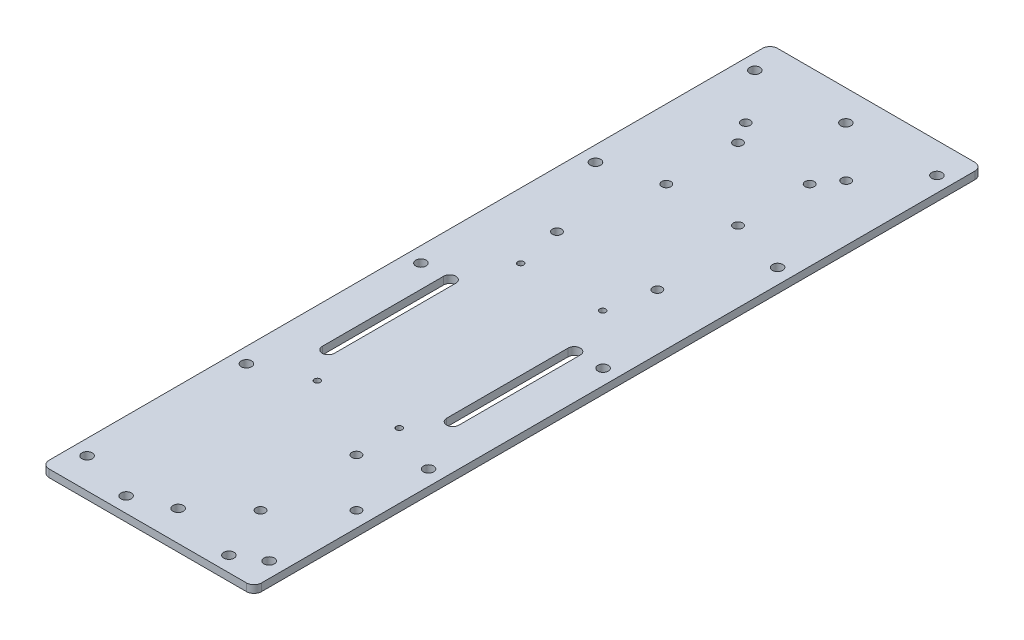
SolidWorks part; units mm, degrees
ref_plane "Front Plane" through (0, 0, 0) normal (0, 0, 1) x (1, 0, 0)
ref_plane "Top Plane" through (0, 0, 0) normal (0, 1, 0) x (1, 0, 0)
ref_plane "Right Plane" through (0, 0, 0) normal (1, 0, 0) x (0, 0, -1)
sketch "Sketch2" plane through (0, 0, 0) normal (0, 1, 0) x (1, 0, 0)
  line L0 (-44.45, 0) -> (44.45, 0) construction
  line L1 (-41.275, 152.4) -> (41.275, 152.4)
  line L2 (-44.45, 149.225) -> (-44.45, -149.225)
  line L3 (-41.275, -152.4) -> (41.275, -152.4)
  line L4 (44.45, 149.225) -> (44.45, -149.225)
  line L5 (0, 152.4) -> (0, -152.4) construction
  arc A0 (-44.45, -149.225) -> (-41.275, -152.4) centre (-41.275, -149.225) ccw
  arc A1 (41.275, -152.4) -> (44.45, -149.225) centre (41.275, -149.225) ccw
  arc A2 (41.275, 152.4) -> (44.45, 149.225) centre (41.275, 149.225) cw
  arc A3 (-41.275, 152.4) -> (-44.45, 149.225) centre (-41.275, 149.225) ccw
  point P8 (0, 0)
  point P13 (-44.45, -152.4)
  point P16 (44.45, -152.4)
  point P21 (-44.45, 152.4)
  dimension "D3" = 3.175
  dimension "D1" = 304.8
  dimension "D2" = 88.9
extrude "Plate Thickness" add sketch "Sketch2" along normal blind 3.175 contours L2 A0 L3 A1 L4 A2 L1 A3
sketch "Sketch10" plane through (0, 3.175, 0) normal (0, 1, 0) x (1, 0, 0)
  line L1 (41.275, 152.4) -> (177.986, 152.4)
  line L2 (41.275, 152.4) -> (41.275, 127)
  line L3 (41.275, 127) -> (177.986, 127)
  line L5 (44.45, 149.225) -> (44.45, -149.225) construction
  line L6 (0, 0) -> (0, 234.1968) construction
  line L7 (0, 0) -> (254.2756, 0) construction
  line L8 (41.275, -127) -> (177.986, -127)
  line L9 (41.275, -152.4) -> (41.275, -127)
  line L10 (41.275, -152.4) -> (177.986, -152.4)
  line L11 (41.275, 152.4) -> (177.986, 152.4)
  line L12 (41.275, 152.4) -> (41.275, 127)
  line L13 (41.275, 127) -> (177.986, 127)
  line L14 (41.275, -127) -> (177.986, -127)
  line L15 (41.275, -152.4) -> (41.275, -127)
  line L16 (41.275, -152.4) -> (177.986, -152.4)
  line L17 (41.275, 152.4) -> (177.986, 152.4)
  line L18 (41.275, 152.4) -> (41.275, 127)
  line L19 (41.275, 127) -> (177.986, 127)
  line L20 (41.275, -127) -> (177.986, -127)
  line L21 (41.275, -152.4) -> (41.275, -127)
  line L22 (41.275, -152.4) -> (177.986, -152.4)
  line L23 (41.275, 152.4) -> (177.986, 152.4)
  line L24 (41.275, 152.4) -> (41.275, 127)
  line L25 (41.275, 127) -> (177.986, 127)
  line L26 (41.275, -127) -> (177.986, -127)
  line L27 (41.275, -152.4) -> (41.275, -127)
  line L28 (41.275, -152.4) -> (177.986, -152.4)
  line L29 (-41.275, -127) -> (-177.986, -127)
  line L30 (-41.275, -152.4) -> (-41.275, -127)
  line L31 (-41.275, -152.4) -> (-177.986, -152.4)
  line L32 (-41.275, 127) -> (-177.986, 127)
  line L33 (-41.275, 152.4) -> (-41.275, 127)
  line L34 (-41.275, 152.4) -> (-177.986, 152.4)
  arc A0 (177.986, 127) -> (177.986, 152.4) centre (184.15, 139.7) ccw
  arc A1 (177.986, -127) -> (177.986, -152.4) centre (184.15, -139.7) cw
  arc A2 (177.986, 127) -> (177.986, 152.4) centre (184.15, 139.7) ccw
  arc A3 (177.986, -127) -> (177.986, -152.4) centre (184.15, -139.7) cw
  arc A4 (177.986, 127) -> (177.986, 152.4) centre (184.15, 139.7) ccw
  arc A5 (177.986, -127) -> (177.986, -152.4) centre (184.15, -139.7) cw
  arc A6 (177.986, 127) -> (177.986, 152.4) centre (184.15, 139.7) ccw
  arc A7 (177.986, -127) -> (177.986, -152.4) centre (184.15, -139.7) cw
  arc A8 (-177.986, -127) -> (-177.986, -152.4) centre (-184.15, -139.7) ccw
  arc A9 (-177.986, 127) -> (-177.986, 152.4) centre (-184.15, 139.7) cw
  arc M45 (-41.275, 152.4) -> (-44.45, 149.225) centre (-41.275, 149.225) ccw
  line M46 (-44.45, 149.225) -> (-44.45, -149.225)
  arc M47 (-44.45, -149.225) -> (-41.275, -152.4) centre (-41.275, -149.225) ccw
  arc M49 (41.275, -152.4) -> (44.45, -149.225) centre (41.275, -149.225) ccw
  line M50 (44.45, -149.225) -> (44.45, 149.225)
  arc M51 (44.45, 149.225) -> (41.275, 152.4) centre (41.275, 149.225) ccw
  dimension "D1" = 139.7
  dimension "D2" = 25.4
extrude "Boss-Extrude1" [suppressed] add sketch "Sketch10" against normal up to surface (3.175 mm away) contours A9 L32 L34 M46 M45 | L3 A0 L1 M51 M50 | A1 L8 L10 M50 M49 | L29 A8 L31 M47 M46 up to face at (0, 0, 0)
sketch "Sketch3" plane through (0, 3.175, 0) normal (0, 1, 0) x (1, 0, 0)
  line L0 (-44.45, 149.225) -> (-44.45, -149.225) construction
  line L1 (-41.275, 152.4) -> (41.275, 152.4) construction
  line L2 (-44.45, 0) -> (152.1758, 0) construction
  line L3 (-44.45, 149.225) -> (-44.45, -149.225) construction
  line L4 (0, 152.4) -> (0, -152.4) construction
  line L5 (-41.275, -152.4) -> (41.275, -152.4) construction
  line L6 (-41.275, -152.4) -> (41.275, -152.4) construction
  circle A0 centre (-38.1, 139.7) radius 2.159
  circle A1 centre (-38.1, 73.025) radius 2.159
  circle A2 centre (-38.1, -73.025) radius 2.159
  circle A3 centre (-38.1, -139.7) radius 2.159
  circle A4 centre (38.1, -139.7) radius 2.159
  circle A5 centre (38.1, -73.025) radius 2.159
  circle A6 centre (38.1, 73.025) radius 2.159
  circle A7 centre (38.1, 139.7) radius 2.159
  circle A8 centre (0, 139.7) radius 2.159
  circle A9 centre (0, -139.7) radius 2.159
  circle A10 centre (-38.1, 0) radius 2.159
  circle A11 centre (38.1, 0) radius 2.159
  dimension "D1" = 4.318
  dimension "D4" = 4.318
  dimension "D2" = 6.35
  dimension "D3" = 12.7
  dimension "D5" = 12.7
  dimension "D6" = 12.7
extrude "Mounting holes" cut sketch "Sketch3" against normal through all
sketch "Sketch4" plane through (0, 3.175, 0) normal (0, 1, 0) x (1, 0, 0)
  line L0 (-21.0058, 39.8143) -> (21.0058, 39.8143) construction
  line L1 (0, 0) -> (0, 139.7) construction
  circle A0 centre (-21.0058, 118.8083) radius 1.905
  circle A1 centre (-21.0058, 39.8143) radius 1.905
  circle A2 centre (21.0058, 39.8143) radius 1.905
  circle A3 centre (21.0058, 118.8083) radius 1.905
  point P13 (0, 39.8143)
  point P17 (0, 69.85)
  point P18 (0, 69.85)
  dimension "D1" = 3.81
  dimension "D2" = 78.994
  dimension "D3" = 42.0116
extrude "Jetson Holes (w/o mount)" cut sketch "Sketch4" against normal through all
sketch "Sketch5" plane through (0, 3.175, 0) normal (0, 1, 0) x (1, 0, 0)
  circle A1 centre (-15.3784, 109.9339) radius 1.905
  circle A3 centre (14.619, 109.9339) radius 1.905
  circle A4 centre (14.619, 79.9365) radius 1.905
  circle A5 centre (-15.3784, 79.9365) radius 1.905
  dimension "D1" = 3.81
  dimension "D2" = 29.9974
  dimension "D3" = 29.9974
extrude "PDB holes" cut sketch "Sketch5" against normal through all
sketch "Sketch6" plane through (0, 3.175, 0) normal (0, 1, 0) x (1, 0, 0)
  circle A6 centre (38.0032, -103.0828) radius 1.905
  circle A7 centre (17.9372, -83.0168) radius 1.905
  circle A8 centre (17.9372, -123.1488) radius 1.905
  dimension "D5" = 3.81
  dimension "D6" = 40.132
  dimension "D7" = 20.066
  dimension "D8" = 20.066
extrude "Lidar Holes" cut sketch "Sketch6" against normal through all
sketch "Sketch7" plane through (0, 3.175, 0) normal (0, 1, 0) x (1, 0, 0)
  line L0 (0, 152.4) -> (0, -152.4) construction
  line L1 (-41.275, 152.4) -> (41.275, 152.4) construction
  line L2 (-41.275, -152.4) -> (41.275, -152.4) construction
  line L3 (17.145, 20.7699) -> (-17.145, 20.7699) construction
  circle A0 centre (-17.145, 20.7699) radius 1.27
  circle A1 centre (-17.145, -64.3201) radius 1.27
  circle A2 centre (17.145, -64.3201) radius 1.27
  circle A3 centre (17.145, 20.7699) radius 1.27
  point P14 (0, 20.7699)
  dimension "D1" = 2.54
  dimension "D2" = 85.09
  dimension "D3" = 34.29
extrude "PixHawk Holes" cut sketch "Sketch7" against normal through all
sketch "Sketch8" plane through (0, 3.175, 0) normal (0, 1, 0) x (1, 0, 0)
  line L0 (0, 152.4) -> (0, -115.5095) construction
  line L1 (-41.275, 152.4) -> (41.275, 152.4) construction
  line L2 (-26.035, -0.006) -> (-26.035, -50.806) construction
  line L3 (-23.495, -0.006) -> (-23.495, -50.806)
  line L4 (-28.575, -0.006) -> (-28.575, -50.806)
  line L5 (26.035, -0.006) -> (26.035, -50.806) construction
  line L6 (23.495, -0.006) -> (23.495, -50.806)
  line L7 (28.575, -0.006) -> (28.575, -50.806)
  arc A0 (-23.495, -0.006) -> (-28.575, -0.006) centre (-26.035, -0.006) ccw
  arc A1 (-28.575, -50.806) -> (-23.495, -50.806) centre (-26.035, -50.806) ccw
  arc A2 (23.495, -0.006) -> (28.575, -0.006) centre (26.035, -0.006) cw
  arc A3 (28.575, -50.806) -> (23.495, -50.806) centre (26.035, -50.806) cw
  point P7 (-26.035, -25.406)
  point P14 (26.035, -25.406)
  dimension "D1" = 50.8
  dimension "D2" = 5.08
  dimension "D3" = 26.035
extrude "Battery Holes" cut sketch "Sketch8" against normal through all
sketch "Sketch9" plane through (0, 3.175, 0) normal (0, 1, 0) x (1, 0, 0)
  line L0 (-41.275, -152.4) -> (41.275, -152.4) construction
  line L1 (-41.275, 152.4) -> (41.275, 152.4) construction
  line L2 (-43.782, -152.4) -> (43.782, -152.4) construction
  line L3 (-43.782, -152.4) -> (-43.782, -139.298) construction
  line L4 (-43.782, -139.298) -> (43.782, -139.298) construction
  line L5 (43.782, -152.4) -> (43.782, -139.298) construction
  circle A0 centre (-15.4076, -146.05) radius 2.159
  circle A1 centre (27.592, -146.05) radius 2.159
  point P10 (0, -139.298)
  point P13 (0, 152.4)
  dimension "D1" = 4.318
  dimension "D2" = 4.318
  dimension "D3" = 42.9997
  dimension "D4" = 6.35
  dimension "D5" = 87.564
  dimension "D6" = 16.19
extrude "Stereo Cam" cut sketch "Sketch9" against normal through all contours A0 | A1
sketch "Sketch11" plane through (0, 3.175, 0) normal (0, 1, 0) x (1, 0, 0)
  line L0 (173.65, 139.7) -> (175.65, 139.7) construction
  line L1 (173.65, 140.95) -> (175.65, 140.95)
  line L2 (173.65, 138.45) -> (175.65, 138.45)
  line L3 (184.15, 139.7) -> (184.15, 143.0164) construction
  line L4 (194.65, 139.7) -> (192.65, 139.7) construction
  line L5 (194.65, 140.95) -> (192.65, 140.95)
  line L6 (194.65, 138.45) -> (192.65, 138.45)
  line L7 (184.15, 148.7) -> (184.15, 146.7) construction
  line L8 (185.4, 148.7) -> (185.4, 146.7)
  line L9 (182.9, 148.7) -> (182.9, 146.7)
  line L10 (184.15, 139.7) -> (199.8184, 139.7) construction
  line L11 (184.15, 130.7) -> (184.15, 132.7) construction
  line L12 (185.4, 130.7) -> (185.4, 132.7)
  line L13 (182.9, 130.7) -> (182.9, 132.7)
  line L14 (44.45, 149.225) -> (44.45, -149.225) construction
  line L15 (-41.275, 152.4) -> (41.275, 152.4) construction
  line L16 (0, 0) -> (0, 273.2731) construction
  line L19 (0, 0) -> (202.4297, 0) construction
  line L22 (184.15, -139.7) -> (199.8184, -139.7) construction
  line L25 (184.15, -139.7) -> (184.15, -143.0164) construction
  line L28 (184.15, -130.7) -> (184.15, -132.7) construction
  line L29 (185.4, -130.7) -> (185.4, -132.7)
  line L30 (182.9, -130.7) -> (182.9, -132.7)
  line L33 (184.15, -148.7) -> (184.15, -146.7) construction
  line L36 (185.4, -148.7) -> (185.4, -146.7)
  line L39 (182.9, -148.7) -> (182.9, -146.7)
  line L42 (194.65, -139.7) -> (192.65, -139.7) construction
  line L43 (194.65, -140.95) -> (192.65, -140.95)
  line L44 (194.65, -138.45) -> (192.65, -138.45)
  line L45 (173.65, -139.7) -> (175.65, -139.7) construction
  line L46 (173.65, -140.95) -> (175.65, -140.95)
  line L49 (173.65, -138.45) -> (175.65, -138.45)
  line L52 (-184.15, -139.7) -> (-184.15, -143.0164) construction
  line L55 (-184.15, -139.7) -> (-199.8184, -139.7) construction
  line L58 (-173.65, -139.7) -> (-175.65, -139.7) construction
  line L59 (-173.65, -140.95) -> (-175.65, -140.95)
  line L60 (-173.65, -138.45) -> (-175.65, -138.45)
  line L61 (-184.15, -148.7) -> (-184.15, -146.7) construction
  line L62 (-185.4, -148.7) -> (-185.4, -146.7)
  line L63 (-182.9, -148.7) -> (-182.9, -146.7)
  line L64 (-184.15, -130.7) -> (-184.15, -132.7) construction
  line L65 (-185.4, -130.7) -> (-185.4, -132.7)
  line L66 (-182.9, -130.7) -> (-182.9, -132.7)
  line L67 (-194.65, -139.7) -> (-192.65, -139.7) construction
  line L68 (-194.65, -140.95) -> (-192.65, -140.95)
  line L69 (-194.65, -138.45) -> (-192.65, -138.45)
  line L70 (-184.15, 139.7) -> (-199.8184, 139.7) construction
  line L71 (-184.15, 139.7) -> (-184.15, 143.0164) construction
  line L72 (-184.15, 130.7) -> (-184.15, 132.7) construction
  line L73 (-185.4, 130.7) -> (-185.4, 132.7)
  line L74 (-182.9, 130.7) -> (-182.9, 132.7)
  line L75 (-184.15, 148.7) -> (-184.15, 146.7) construction
  line L76 (-185.4, 148.7) -> (-185.4, 146.7)
  line L77 (-182.9, 148.7) -> (-182.9, 146.7)
  line L78 (-194.65, 139.7) -> (-192.65, 139.7) construction
  line L79 (-194.65, 140.95) -> (-192.65, 140.95)
  line L80 (-194.65, 138.45) -> (-192.65, 138.45)
  line L81 (-173.65, 139.7) -> (-175.65, 139.7) construction
  line L82 (-173.65, 140.95) -> (-175.65, 140.95)
  line L83 (-173.65, 138.45) -> (-175.65, 138.45)
  circle A0 centre (184.15, 139.7) radius 2.5
  arc A1 (173.65, 140.95) -> (173.65, 138.45) centre (173.65, 139.7) ccw
  arc A2 (175.65, 138.45) -> (175.65, 140.95) centre (175.65, 139.7) ccw
  arc A4 (194.65, 140.95) -> (194.65, 138.45) centre (194.65, 139.7) cw
  arc A5 (192.65, 138.45) -> (192.65, 140.95) centre (192.65, 139.7) cw
  arc A6 (185.4, 148.7) -> (182.9, 148.7) centre (184.15, 148.7) ccw
  arc A7 (182.9, 146.7) -> (185.4, 146.7) centre (184.15, 146.7) ccw
  arc A8 (185.4, 130.7) -> (182.9, 130.7) centre (184.15, 130.7) cw
  arc A9 (182.9, 132.7) -> (185.4, 132.7) centre (184.15, 132.7) cw
  circle A37 centre (184.15, -139.7) radius 2.5
  arc A38 (185.4, -130.7) -> (182.9, -130.7) centre (184.15, -130.7) ccw
  arc A39 (182.9, -132.7) -> (185.4, -132.7) centre (184.15, -132.7) ccw
  arc A40 (185.4, -148.7) -> (182.9, -148.7) centre (184.15, -148.7) cw
  arc A41 (182.9, -146.7) -> (185.4, -146.7) centre (184.15, -146.7) cw
  arc A42 (194.65, -140.95) -> (194.65, -138.45) centre (194.65, -139.7) ccw
  arc A43 (192.65, -138.45) -> (192.65, -140.95) centre (192.65, -139.7) ccw
  arc A44 (173.65, -140.95) -> (173.65, -138.45) centre (173.65, -139.7) cw
  arc A45 (175.65, -138.45) -> (175.65, -140.95) centre (175.65, -139.7) cw
  circle A46 centre (-184.15, -139.7) radius 2.5
  arc A47 (-173.65, -140.95) -> (-173.65, -138.45) centre (-173.65, -139.7) ccw
  arc A48 (-175.65, -138.45) -> (-175.65, -140.95) centre (-175.65, -139.7) ccw
  arc A49 (-185.4, -148.7) -> (-182.9, -148.7) centre (-184.15, -148.7) ccw
  arc A50 (-182.9, -146.7) -> (-185.4, -146.7) centre (-184.15, -146.7) ccw
  arc A51 (-185.4, -130.7) -> (-182.9, -130.7) centre (-184.15, -130.7) cw
  arc A52 (-182.9, -132.7) -> (-185.4, -132.7) centre (-184.15, -132.7) cw
  arc A53 (-194.65, -140.95) -> (-194.65, -138.45) centre (-194.65, -139.7) cw
  arc A54 (-192.65, -138.45) -> (-192.65, -140.95) centre (-192.65, -139.7) cw
  circle A55 centre (-184.15, 139.7) radius 2.5
  arc A56 (-185.4, 130.7) -> (-182.9, 130.7) centre (-184.15, 130.7) ccw
  arc A57 (-182.9, 132.7) -> (-185.4, 132.7) centre (-184.15, 132.7) ccw
  arc A58 (-185.4, 148.7) -> (-182.9, 148.7) centre (-184.15, 148.7) cw
  arc A59 (-182.9, 146.7) -> (-185.4, 146.7) centre (-184.15, 146.7) cw
  arc A60 (-194.65, 140.95) -> (-194.65, 138.45) centre (-194.65, 139.7) ccw
  arc A61 (-192.65, 138.45) -> (-192.65, 140.95) centre (-192.65, 139.7) ccw
  arc A62 (-173.65, 140.95) -> (-173.65, 138.45) centre (-173.65, 139.7) cw
  arc A63 (-175.65, 138.45) -> (-175.65, 140.95) centre (-175.65, 139.7) cw
  point P5 (174.65, 139.7)
  point P16 (193.65, 139.7)
  point P23 (184.15, 147.7)
  point P31 (184.15, 131.7)
  point P47 (184.15, -131.7)
  point P54 (184.15, -147.7)
  point P61 (193.65, -139.7)
  point P68 (174.65, -139.7)
  point P79 (-174.65, -139.7)
  point P86 (-184.15, -147.7)
  point P93 (-184.15, -131.7)
  point P100 (-193.65, -139.7)
  point P111 (-184.15, 131.7)
  point P118 (-184.15, 147.7)
  point P125 (-193.65, 139.7)
  point P132 (-174.65, 139.7)
  dimension "D1" = 5
  dimension "D2" = 2.5
  dimension "D3" = 2
  dimension "D4" = 19
  dimension "D5" = 2.5
  dimension "D6" = 2
  dimension "D7" = 16
  dimension "D8" = 139.7
  dimension "D9" = 12.7
extrude "motor mounting" [suppressed] cut sketch "Sketch11" against normal through all
